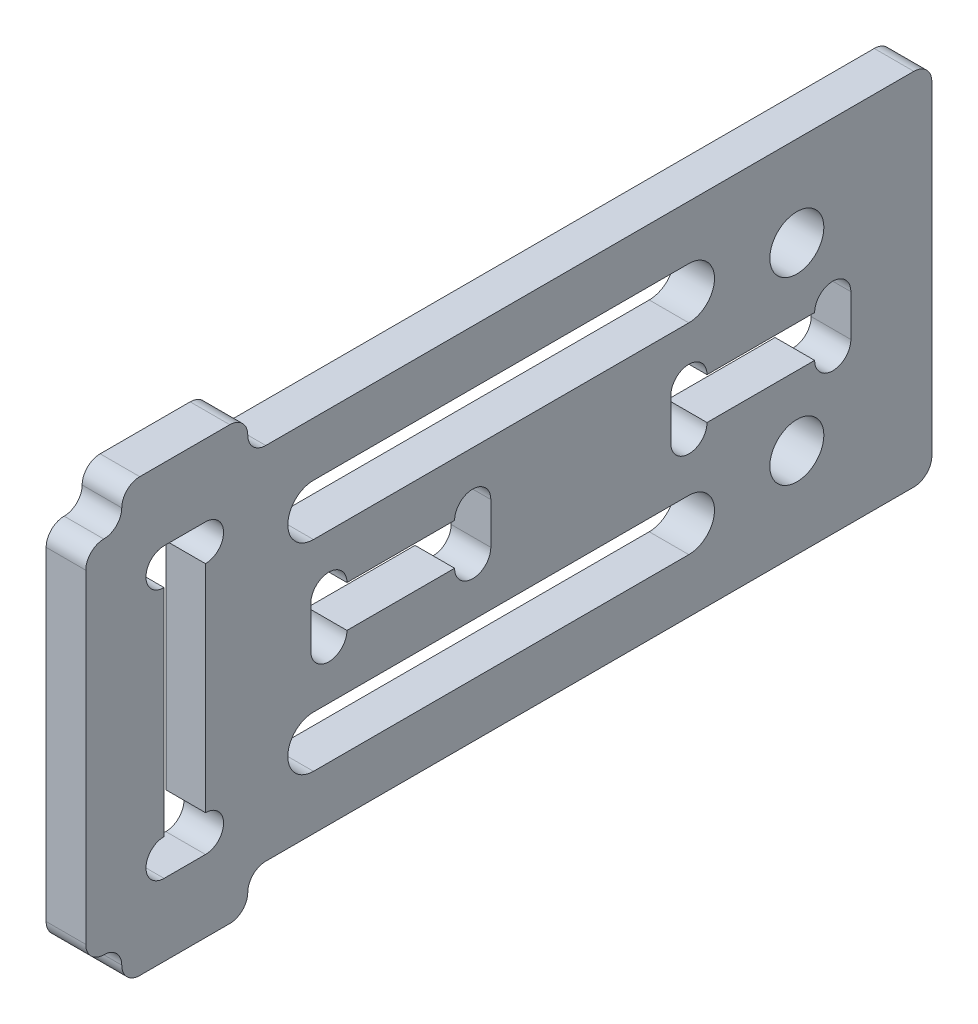
SolidWorks part; units mm, degrees
material "Thornel Mat VMA"
ref_plane "前视基准面" through (0, 0, 0) normal (0, 0, 1) x (1, 0, 0)
ref_plane "上视基准面" through (0, 0, 0) normal (0, 1, 0) x (1, 0, 0)
ref_plane "右视基准面" through (0, 0, 0) normal (1, 0, 0) x (0, 0, -1)
sketch "草图1" plane through (0, 0, 0) normal (1, 0, 0) x (0, 0, -1)
  line L0 (8.5, 10) -> (8.5, -10) construction
  line L1 (23.5, -10) -> (-14.5, -10)
  line L2 (23.5, -10) -> (23.5, 10)
  line L3 (23.5, 10) -> (-14.5, 10)
  line L4 (-23.5, -10) -> (-23.5, 10)
  line L5 (23.5, -10) -> (-23.5, 10) construction
  line L6 (23.5, 10) -> (-23.5, -10) construction
  line L7 (16, 10) -> (16, -10) construction
  line L8 (0, 0) -> (23.5, 0) construction
  line L9 (-21.5, 10) -> (-21.5, 12)
  line L10 (-1, -1.15) -> (-11, -1.15)
  line L11 (-1, -1.15) -> (-1, 1.15)
  line L12 (-1, 1.15) -> (-11, 1.15)
  line L13 (-11, -1.15) -> (-11, 1.15)
  line L14 (-1, -1.15) -> (-11, 1.15) construction
  line L15 (-1, 1.15) -> (-11, -1.15) construction
  line L16 (-16.85, -8) -> (-19.15, -8)
  line L17 (-16.85, -8) -> (-16.85, 8)
  line L18 (-16.85, 8) -> (-19.15, 8)
  line L19 (-19.15, -8) -> (-19.15, 8)
  line L20 (-16.85, -8) -> (-19.15, 8) construction
  line L21 (-16.85, 8) -> (-19.15, -8) construction
  line L22 (-21.5, 12) -> (-14.5, 12)
  line L23 (-14.5, 12) -> (-14.5, 10)
  line L24 (-18, 8) -> (-18, 12) construction
  line L25 (-21.5, 10) -> (-23.5, 10)
  line L26 (-14.5, -12) -> (-14.5, -10)
  line L27 (-21.5, -12) -> (-14.5, -12)
  line L28 (-21.5, -10) -> (-21.5, -12)
  line L29 (-21.5, -10) -> (-23.5, -10)
  line L30 (-10.85, 5.575) -> (10, 5.575) construction
  line L31 (19, -1.15) -> (9, -1.15)
  line L32 (19, -1.15) -> (19, 1.15)
  line L33 (19, 1.15) -> (9, 1.15)
  line L34 (9, -1.15) -> (9, 1.15)
  line L35 (19, -1.15) -> (9, 1.15) construction
  line L36 (19, 1.15) -> (9, -1.15) construction
  line L37 (-10.85, 7) -> (10, 7)
  line L38 (-10.85, 4.15) -> (10, 4.15)
  line L39 (-10.85, -5.575) -> (10, -5.575) construction
  line L40 (-10.85, -7) -> (10, -7)
  line L41 (-10.85, -4.15) -> (10, -4.15)
  circle A0 centre (16, 5) radius 1.5
  circle A1 centre (16, -5) radius 1.5
  circle A2 centre (-19.15, 6.995) radius 1.005
  circle A3 centre (-16.85, 6.995) radius 1.005
  circle A4 centre (-16.85, -6.995) radius 1.005
  circle A5 centre (-19.15, -6.995) radius 1.005
  circle A6 centre (-9.995, 1.15) radius 1.005
  circle A7 centre (-9.995, -1.15) radius 1.005
  circle A8 centre (-2.005, -1.15) radius 1.005
  circle A9 centre (-2.005, 1.15) radius 1.005
  circle A10 centre (10.005, 1.15) radius 1.005
  circle A11 centre (17.995, 1.15) radius 1.005
  circle A12 centre (17.995, -1.15) radius 1.005
  circle A13 centre (10.005, -1.15) radius 1.005
  circle A14 centre (16, 5) radius 2.75 construction
  arc A15 (-10.85, 7) -> (-10.85, 4.15) centre (-10.85, 5.575) ccw
  arc A16 (10, 4.15) -> (10, 7) centre (10, 5.575) ccw
  arc A17 (-10.85, -7) -> (-10.85, -4.15) centre (-10.85, -5.575) cw
  arc A18 (10, -4.15) -> (10, -7) centre (10, -5.575) cw
  point P0 (0, 0)
  point P16 (-18, 0)
  point P17 (-6, 0)
  point P52 (14, 0)
  point P68 (-0.425, 5.575)
  point P75 (-0.425, -5.575)
  dimension "D6" = 3
  dimension "D12" = 2.01
  dimension "D16" = 5.5
  dimension "D1" = 20
  dimension "D2" = 47
  dimension "D3" = 15
  dimension "D4" = 7.5
  dimension "D5" = 10
  dimension "D7" = 10
  dimension "D8" = 16
  dimension "D9" = 26.5
  dimension "D10" = 2.3
  dimension "D11" = 12
  dimension "D13" = 7
  dimension "D14" = 2
  dimension "D15" = 20
  dimension "D17" = 3
  dimension "D18" = 3
  dimension "D19" = 6
  dimension "D20" = 6
extrude "凸台-拉伸1" add sketch "草图1" along normal blind 2.2 contours L4 L1 L2 L3 A9 L11 A8 L10 A7 L13 A6 L12 A5 L19 A2 L18 A3 L17 A4 L16 A1 A0 region at (0, 0, 0.1838)
fillet "圆角1" radius 1 12 edges at (1.1, -10, 23.5) (1.1, 10, 23.5) (1.1, 12, 14.5) (1.1, 10, 14.5) (1.1, 10, -23.5) (1.1, -10, -23.5) (1.1, -10, 14.5) (1.1, -12, 14.5) (1.1, -12, 21.5) (1.1, -10, 21.5) (1.1, 12, 21.5) (1.1, 10, 21.5)
